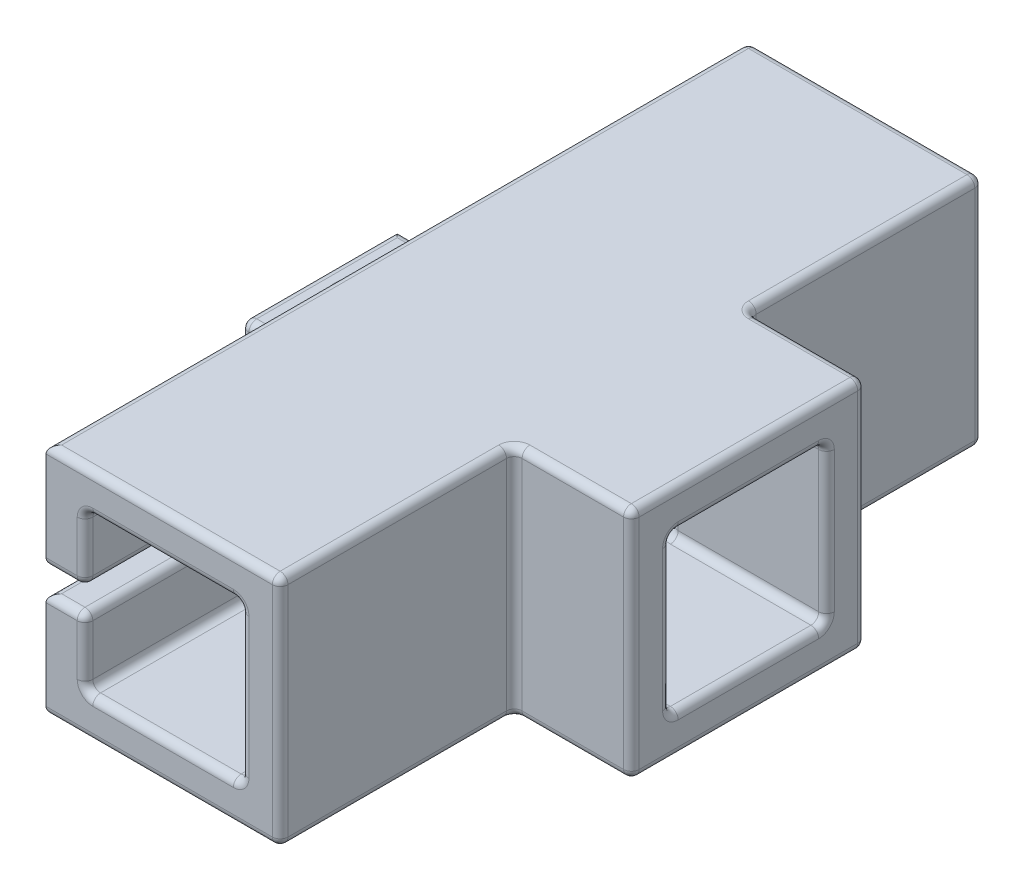
SolidWorks part; units mm, degrees
ref_plane "Front Plane" through (0, 0, 0) normal (0, 0, 1) x (1, 0, 0)
ref_plane "Top Plane" through (0, 0, 0) normal (0, 1, 0) x (1, 0, 0)
ref_plane "Right Plane" through (0, 0, 0) normal (1, 0, 0) x (0, 0, -1)
sketch "Sketch1" plane through (0, 0, 0) normal (0, 0, 1) x (1, 0, 0)
  line L0 (-5.8424, 8.1021) -> (-5.8424, -11.8979)
  line L1 (-10.8424, 13.1021) -> (19.1576, 13.1021)
  line L2 (-10.8424, 13.1021) -> (-10.8424, -16.8979)
  line L3 (-10.8424, -16.8979) -> (19.1576, -16.8979)
  line L4 (19.1576, 13.1021) -> (19.1576, -16.8979)
  line L5 (-5.8424, -11.8979) -> (14.1576, -11.8979)
  line L6 (14.1576, 8.1021) -> (14.1576, -11.8979)
  line L7 (-5.8424, 8.1021) -> (14.1576, 8.1021)
  dimension "D1" = 30
  dimension "D2" = 30
  dimension "D3" = 5
extrude "Boss-Extrude1" add sketch "Sketch1" along normal blind 90
sketch "Sketch2" plane through (19.1576, 0, 0) normal (1, 0, 0) x (0, 0, -1)
  line L0 (-45, 13.1021) -> (-30, 13.1021)
  line L1 (-90, 13.1021) -> (0, 13.1021) construction
  line L2 (-30, 13.1021) -> (-30, -16.8979)
  line L3 (-90, -16.8979) -> (0, -16.8979) construction
  line L4 (-30, -16.8979) -> (-60, -16.8979)
  line L5 (-60, -16.8979) -> (-60, 13.1021)
  line L6 (-60, 13.1021) -> (-45, 13.1021)
  line L7 (-55, 8.1021) -> (-45, 8.1021)
  line L8 (-45, 8.1021) -> (-35, 8.1021)
  line L9 (-35, 8.1021) -> (-35, -11.8979)
  line L10 (-35, -11.8979) -> (-55, -11.8979)
  line L11 (-55, -11.8979) -> (-55, 8.1021)
  dimension "D1" = 5
extrude "Boss-Extrude2" add sketch "Sketch2" along normal blind 30 contours L6 L0 L2 L4 L5 | L7 L8 L9 L10 L11
sketch "Sketch3" plane through (19.1576, 0, 0) normal (1, 0, 0) x (0, 0, -1)
  line L0 (-55, 8.1021) -> (-35, 8.1021)
  line L1 (-35, 8.1021) -> (-35, -11.8979)
  line L2 (-35, -11.8979) -> (-55, -11.8979)
  line L3 (-55, -11.8979) -> (-55, 8.1021)
extrude "Cut-Extrude1" cut sketch "Sketch3" against normal blind 6
sketch "Sketch4" plane through (0, 0, 0) normal (0, 0, -1) x (-1, 0, 0)
  line L0 (5.8424, -11.8979) -> (5.8424, -1.8979)
  line L1 (5.8424, 8.1021) -> (5.8424, -11.8979) construction
  line L2 (5.8424, -1.8979) -> (5.8424, -0.3979)
  line L3 (5.8424, -0.3979) -> (10.8424, -0.3979)
  line L4 (10.8424, 13.1021) -> (10.8424, -16.8979) construction
  line L5 (10.8424, -0.3979) -> (20.8424, -0.3979)
  line L6 (20.8424, -0.3979) -> (20.8424, 4.6021)
  line L7 (20.8424, 4.6021) -> (10.8424, 4.6021)
  line L8 (10.8424, 4.6021) -> (10.8424, -0.3979)
  line L9 (10.8424, -0.3979) -> (10.8424, -3.3979)
  line L10 (10.8424, -3.3979) -> (20.8424, -3.3979)
  line L11 (20.8424, -3.3979) -> (20.8424, -8.3979)
  line L12 (20.8424, -8.3979) -> (10.8424, -8.3979)
  line L13 (10.8424, -8.3979) -> (10.8424, -3.3979)
  line M1 (10.8424, -16.8979) -> (10.8424, 13.1021)
extrude "Boss-Extrude3" add sketch "Sketch4" against normal blind 20 from offset 35 contours L6 L7 L5 M1 | L12 L11 L10 M1 region at (-15.8424, 2.1021, 0) region at (-15.8424, -5.8979, 0) offset against normal yes
sketch "Sketch5" plane through (0, 4.6021, 0) normal (0, 1, 0) x (1, 0, 0)
  line L0 (-20.8424, -35) -> (-10.8424, -55)
  circle A0 centre (-15.8424, -45) radius 2
extrude "Cut-Extrude2" cut sketch "Sketch5" against normal blind 30 contours L0 A0 | L0 A0 region at (-15.0832, 4.6021, 44.6204) region at (-16.6016, 4.6021, 45.3796)
sketch "Sketch6" plane through (0, 0, 90) normal (0, 0, 1) x (1, 0, 0)
  line L0 (-10.8424, -0.3979) -> (-5.8424, -0.3979)
  line L1 (-5.8424, 8.1021) -> (-5.8424, -11.8979) construction
  line L2 (-5.8424, -0.3979) -> (-5.8424, -3.3979)
  line L3 (-5.8424, -3.3979) -> (-10.8424, -3.3979)
  line L4 (-10.8424, 13.1021) -> (-10.8424, -16.8979) construction
  line L5 (-10.8424, -3.3979) -> (-10.8424, -0.3979)
extrude "Cut-Extrude3" cut sketch "Sketch6" against normal blind 140
sketch "Sketch7" plane through (49.1576, 0, 0) normal (1, 0, 0) x (0, 0, -1)
  line L1 (-30, 13.1021) -> (-60, 13.1021)
  line L2 (-30, 13.1021) -> (-30, -16.8979)
  line L3 (-30, -16.8979) -> (-60, -16.8979)
  line L4 (-60, 13.1021) -> (-60, -16.8979)
extrude "Cut-Extrude4" cut sketch "Sketch7" against normal blind 15
fillet "Fillet1" radius 1 54 edges at (-5.8424, -7.6479, 90) (-5.8424, -3.3979, 45) (24.1576, -11.8979, 55) (4.1576, -11.8979, 90) (-5.8424, -11.8979, 45) (24.1576, -11.8979, 35) (14.1576, -1.8979, 90) (14.1576, -11.8979, 72.5) (14.1576, -1.8979, 55) (14.1576, -11.8979, 17.5) (14.1576, -1.8979, 35) (24.1576, 8.1021, 35) (14.1576, 8.1021, 17.5) (4.1576, 8.1021, 90) (14.1576, 8.1021, 72.5) (24.1576, 8.1021, 55) (-5.8424, 3.8521, 90) (-5.8424, 8.1021, 45) (-5.8424, -0.3979, 45) (4.1576, 8.1021, 0) (14.1576, -1.8979, 0) (4.1576, -11.8979, 0) (-5.8424, -7.6479, 0) (-8.3424, -3.3979, 0) (-10.8424, -10.1479, 0) (-10.8424, 6.3521, 0) (-8.3424, -0.3979, 0) (-5.8424, 3.8521, 0) (19.1576, -1.8979, 0) (19.1576, -1.8979, 30) (34.1576, -1.8979, 55) (34.1576, -11.8979, 45) (34.1576, -1.8979, 35) (34.1576, 8.1021, 45) (34.1576, -1.8979, 30) (19.1576, -16.8979, 15) (4.1576, -16.8979, 0) (-10.8424, -16.8979, 45) (4.1576, -16.8979, 90) (34.1576, -16.8979, 45) (26.6576, -16.8979, 30) (26.6576, -16.8979, 60) (34.1576, -1.8979, 60) (19.1576, -1.8979, 90) (19.1576, -1.8979, 60) (19.1576, -16.8979, 75) (19.1576, 13.1021, 75) (4.1576, 13.1021, 90) (-10.8424, 13.1021, 45) (4.1576, 13.1021, 0) (19.1576, 13.1021, 15) (26.6576, 13.1021, 30) (34.1576, 13.1021, 45) (26.6576, 13.1021, 60)
fillet "Fillet2" radius 1 19 edges at (-10.8424, -5.8979, 55) (-10.5495, -3.6908, 0.2929) (-10.8424, -8.3979, 45) (-10.8424, -3.3979, 18) (-10.8424, 2.1021, 55) (-10.8424, 2.1021, 35) (-20.8424, -3.3979, 45) (-20.8424, -5.8979, 55) (-20.8424, -8.3979, 45) (-10.8424, -5.8979, 35) (-15.8424, -3.3979, 35) (-20.8424, -5.8979, 35) (-15.8424, -8.3979, 35) (-10.8424, 4.6021, 45) (-15.8424, 4.6021, 55) (-20.8424, 4.6021, 45) (-15.8424, 4.6021, 35) (-15.8424, 4.6021, 47) (-15.8424, -8.3979, 55)
fillet "Fillet3" radius 1 13 edges at (-20.5495, 4.3092, 54.7071) (-10.5495, -0.105, 0.2929) (-6.1353, -0.105, 89.7071) (-20.8424, 1.6021, 55) (-10.8424, -0.3979, 17.5) (-11.1353, -0.3979, 34.7071) (-16.3424, -0.3979, 35) (-20.8424, -0.3979, 45) (-16.3424, -0.3979, 55) (-11.1353, -0.3979, 55.2929) (-10.8424, -0.3979, 73) (-8.8424, -0.3979, 90) (-13.8424, -0.3979, 45)
fillet "Fillet4" radius 1 8 edges at (-6.1353, -3.6908, 89.7071) (-20.5495, -3.6908, 54.7071) (-15.8424, -3.3979, 43) (-8.8424, -3.3979, 90) (-10.8424, -3.3979, 73) (-11.1353, -3.3979, 55.2929) (-15.8424, -3.3979, 55) (-17.8424, -8.3979, 45)
